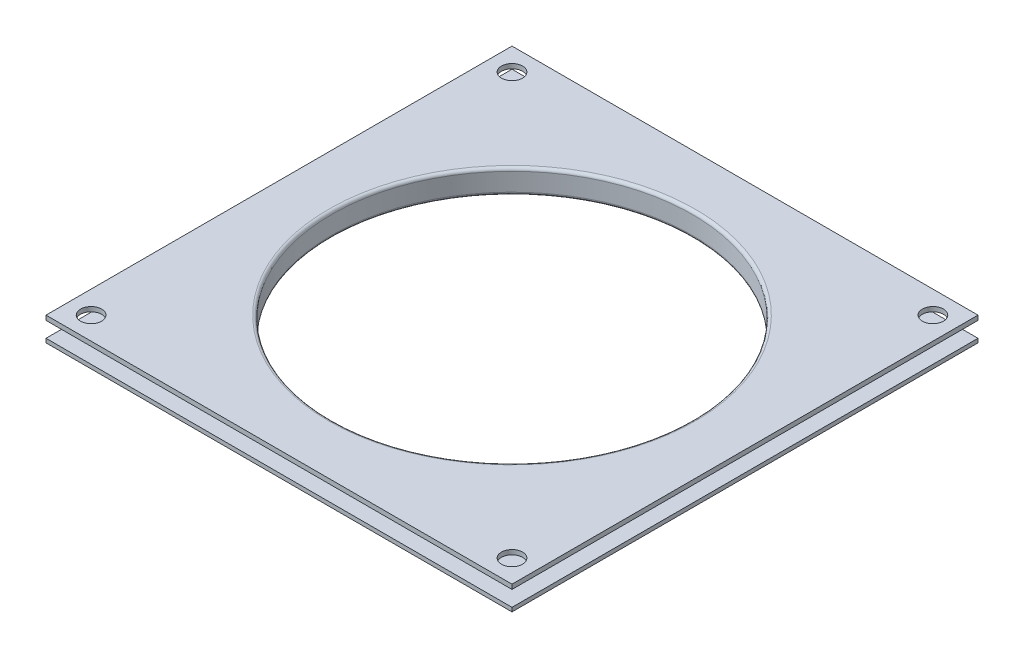
SolidWorks part; units mm, degrees
ref_plane "Alzado" through (0, 0, 0) normal (0, 0, 1) x (1, 0, 0)
ref_plane "Planta" through (0, 0, 0) normal (0, 1, 0) x (1, 0, 0)
ref_plane "Vista lateral" through (0, 0, 0) normal (1, 0, 0) x (0, 0, -1)
sketch "Croquis1" plane through (0, 0, 0) normal (0, 1, 0) x (1, 0, 0)
  line L1 (77.5, -77.5) -> (-77.5, -77.5)
  line L2 (77.5, -77.5) -> (77.5, 77.5)
  line L3 (77.5, 77.5) -> (-77.5, 77.5)
  line L4 (-77.5, -77.5) -> (-77.5, 77.5)
  line L5 (77.5, -77.5) -> (-77.5, 77.5) construction
  line L6 (77.5, 77.5) -> (-77.5, -77.5) construction
  circle A0 centre (0, 0) radius 60
  point P0 (0, 0)
  dimension "D3" = 120
  dimension "D1" = 155
  dimension "D2" = 155
extrude "Saliente-Extruir1" add sketch "Croquis1" along normal blind 8
sketch "Croquis2" plane through (0, 0, 0) normal (0, 0, 1) x (1, 0, 0)
  line L0 (77.5, 8) -> (77.5, 0) construction
  line L1 (63.0578, 6.4741) -> (73.2214, 6.4741)
  line L3 (62.8889, 1.3294) -> (77.5, 1.3294)
  line L8 (77.5, 1.3294) -> (118.6057, 1.3294)
  line L9 (0, 0) -> (0, 13.4766) construction
  line L11 (73.2214, 6.4741) -> (118.6057, 6.4741)
  line L12 (118.6057, 1.3294) -> (118.6057, 6.4741)
  arc A0 (63.0578, 6.4741) -> (62.8889, 1.3294) centre (63.7046, 3.8778) ccw
  point P0 (63.7046, 3.8778)
  point P11 (30.5322, 6.3668)
  point P12 (73.9419, 6.2891)
  point P14 (73.2214, 6.29)
revolve "Cortar-Revolución1" cut sketch "Croquis2" angle 360 about L9
sketch "Croquis3" plane through (0, 8, 0) normal (0, 1, 0) x (1, 0, 0)
  line L4 (-77.5, 77.5) -> (-77.5, -77.5)
  line L5 (-77.5, -77.5) -> (77.5, -77.5)
  line L6 (77.5, -77.5) -> (77.5, 77.5)
  line L7 (77.5, 77.5) -> (-77.5, 77.5)
  line L9 (-77.5, -77.5) -> (77.5, -77.5)
  line L11 (77.5, 77.5) -> (-77.5, 77.5)
  circle A0 centre (70, 70) radius 3.5
  circle A1 centre (-70, 70) radius 3.5
  circle A2 centre (-70, -70) radius 3.5
  circle A3 centre (70, -70) radius 3.5
  dimension "D3" = 7
  dimension "D4" = 7
  dimension "D5" = 7
  dimension "D6" = 7
  dimension "D7" = 70
  dimension "D8" = 140
  dimension "D2" = 140
  dimension "D9" = 140
  dimension "D10" = 70
  dimension "D1" = 0
extrude "Cortar-Extruir4" cut sketch "Croquis3" against normal up to next contours A0 | A1 | A2 | A3
fillet "Redondeo1" radius 1 2 edges at (0, 0, 60) (0, 8, 60)
sketch "Croquis4" plane through (0, 0, 0) normal (0, -1, 0) x (1, 0, 0)
  circle A0 centre (-60, 60) radius 2.5
  circle A1 centre (60, 60) radius 2.5
  circle A2 centre (60, -60) radius 2.5
  circle A3 centre (-60, -60) radius 2.5
  point P0 (0, 0)
  dimension "D3" = 5
  dimension "D4" = 5
  dimension "D5" = 5
  dimension "D6" = 5
  dimension "D1" = 120
  dimension "D2" = 120
extrude "Cortar-Extruir5" cut sketch "Croquis4" against normal up to next
equation "\"D2@Croquis1\"=\"D1@Croquis1\""
equation "\"D3@Croquis1\"=120"
